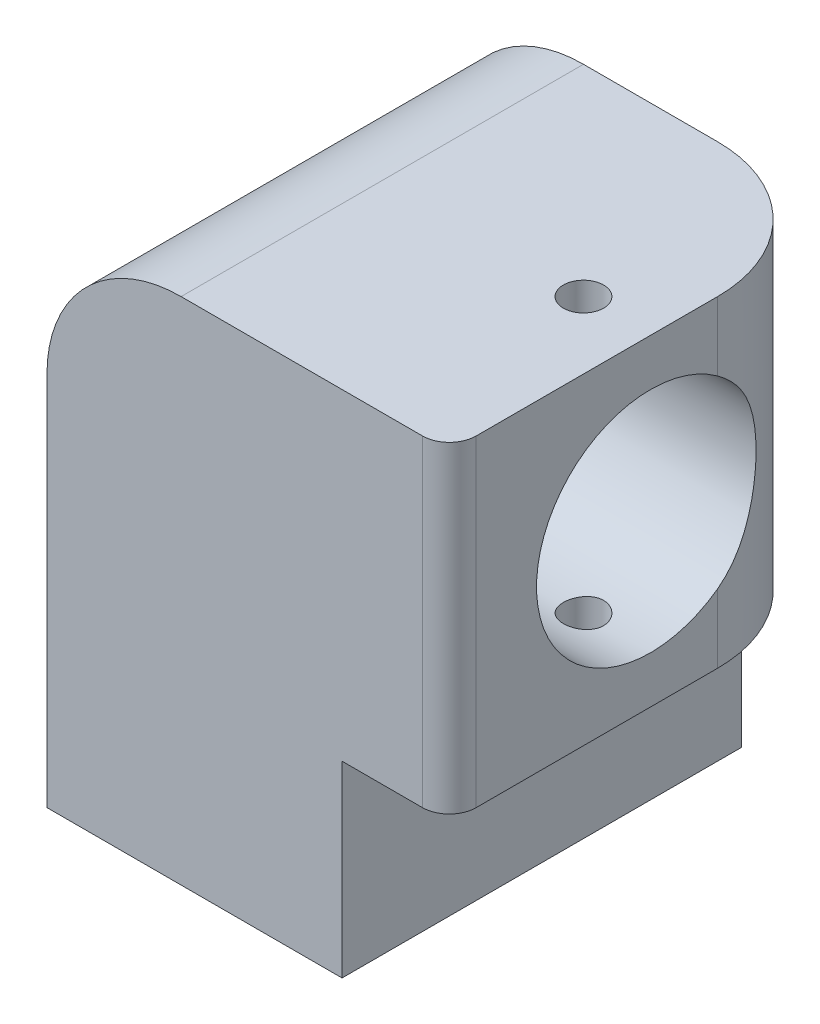
SolidWorks part; units mm, degrees
ref_plane "Alzado" through (0, 0, 0) normal (0, 0, 1) x (1, 0, 0)
ref_plane "Planta" through (0, 0, 0) normal (0, 1, 0) x (1, 0, 0)
ref_plane "Vista lateral" through (0, 0, 0) normal (1, 0, 0) x (0, 0, -1)
sketch "Croquis1" plane through (0, 0, 0) normal (0, 0, 1) x (1, 0, 0)
  line L1 (-15, -12) -> (15, -12)
  line L2 (-15, -12) -> (-15, 12)
  line L3 (-15, 12) -> (15, 12)
  line L4 (15, -12) -> (15, 12)
  line L5 (-15, -12) -> (15, 12) construction
  line L6 (-15, 12) -> (15, -12) construction
  line L7 (-15, -12) -> (7, -12)
  line L8 (-15, -12) -> (-15, -26)
  line L9 (-15, -26) -> (7, -26)
  line L10 (7, -12) -> (7, -26)
  point P0 (0, 0)
  dimension "D1" = 24
  dimension "D2" = 30
  dimension "D3" = 14
  dimension "D4" = 22
extrude "Saliente-Extruir1" add sketch "Croquis1" along normal mid plane 30 contours L1 L4 L3 L2 | L10 L1 L8 L9 region at (0, 0, 0) region at (-4, -19, 0)
sketch "Croquis2" plane through (15, 0, 0) normal (1, 0, 0) x (0, 0, -1)
  circle A0 centre (0, 0) radius 8.5
  dimension "D1" = 17
extrude "Cortar-Extruir1" cut sketch "Croquis2" against normal blind 20
sketch "Croquis4" plane through (0, -26, 0) normal (0, -1, 0) x (1, 0, 0)
  line L0 (-4, 15) -> (-4, -15) construction
  line L1 (-15, 15) -> (7, 15) construction
  line L2 (-15, -15) -> (7, -15) construction
  line L3 (-15, 0) -> (7, 0) construction
  line L4 (-15, 15) -> (-15, -15) construction
  line L5 (7, 15) -> (7, -15) construction
  line L7 (-13, -13) -> (5, -13)
  line L8 (-13, -13) -> (-13, 13)
  line L9 (-13, 13) -> (5, 13)
  line L10 (5, -13) -> (5, 13)
  line L11 (-13, -13) -> (5, 13) construction
  line L12 (-13, 13) -> (5, -13) construction
  point P12 (-4, 0)
  dimension "D1" = 2
  dimension "D2" = 2
extrude "Cortar-Extruir2" cut sketch "Croquis4" against normal blind 2
fillet "Redondeo1" radius 10 1 edges at (-15, 12, 0)
fillet "Redondeo2" radius 10 1 edges at (15, 0, -15)
sketch "Croquis5" plane through (0, 12, 0) normal (0, 1, 0) x (1, 0, 0)
  line L0 (5, -15) -> (5, 15) construction
  line L1 (-17.9999, 0) -> (22.9471, 0) construction
  line L3 (15, -15) -> (15, 5) construction
  circle A1 centre (10, 0) radius 1.5
  dimension "D1" = 5
  dimension "D2" = 3
extrude "Cortar-Extruir3" cut sketch "Croquis5" against normal blind 30
fillet "Redondeo3" radius 2 1 edges at (15, 0, 15)
